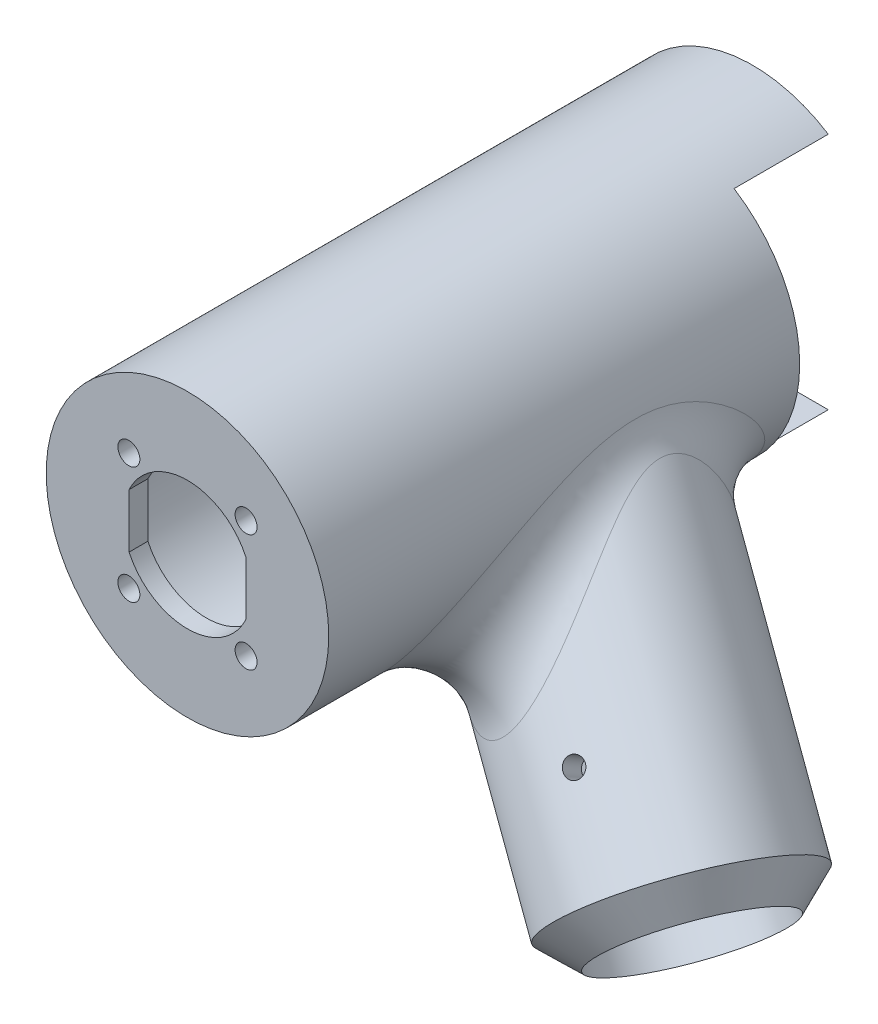
SolidWorks part; units mm, degrees
material "ABS"
ref_plane "Front Plane" through (0, 0, 0) normal (0, 0, 1) x (1, 0, 0)
ref_plane "Top Plane" through (0, 0, 0) normal (0, 1, 0) x (1, 0, 0)
ref_plane "Right Plane" through (0, 0, 0) normal (1, 0, 0) x (0, 0, -1)
sketch "Sketch1" plane through (0, 0, 0) normal (0, 0, 1) x (1, 0, 0)
  circle A0 centre (0, 0) radius 22.5
  dimension "D1" = 45
extrude "Boss-Extrude1" add sketch "Sketch1" along normal blind 90
sketch "Sketch2" plane through (0, 0, 0) normal (0, 0, -1) x (-1, 0, 0)
  circle A0 centre (0, 0) radius 16.2
  circle A1 centre (0, 0) radius 22.5 construction
  dimension "D1" = 6.3
extrude "Cut-Extrude1" cut sketch "Sketch2" against normal offset from surface (87 mm away) 3 up to face at (22.5, 0, 90)
sketch "Sketch3" plane through (0, 0, 0) normal (1, 0, 0) x (0, 0, -1)
  line L1 (15, -19) -> (-15, -19)
  line L2 (15, -19) -> (15, 19)
  line L3 (15, 19) -> (-15, 19)
  line L4 (-15, -19) -> (-15, 19)
  line L5 (15, -19) -> (-15, 19) construction
  line L6 (15, 19) -> (-15, -19) construction
  point P0 (0, 0)
  dimension "D1" = 15
  dimension "D2" = 38
extrude "Cut-Extrude2" cut sketch "Sketch3" along normal blind 33
sketch "Sketch4" plane through (0, 0, 0) normal (1, 0, 0) x (0, 0, -1)
  line L0 (0, 0) -> (-40, 0) construction
  line L1 (0, -22.5) -> (0, 22.5) construction
  line L2 (-10, 15) -> (-60, 15)
  line L3 (-10, 15) -> (-10, -15)
  line L4 (-10, -15) -> (-60, -15)
  line L5 (-60, 15) -> (-60, -15)
  line L6 (-10, 15) -> (-60, -15) construction
  line L7 (-10, -15) -> (-60, 15) construction
  point P2 (-35, 0)
  dimension "D1" = 50
  dimension "D2" = 10
  dimension "D3" = 30
ref_plane "Plane2" through (0, 0, 35) normal (0, 0, -1) x (-1, 0, 0)
sketch3d "3DSketch1"
  line L0 (0, 0, 35) -> (120, -120, 90)
sketch "Sketch5" plane through (0, 0, 35) normal (0, 0, -1) x (-1, 0, 0)
  line L0 (0, 0) -> (-54.3806, -54.3806)
  line L1 (0, 15) -> (0, -15) construction
  dimension "D1" = 45
ref_plane "Plane3" through (0, 0, 35) normal (0.6727, -0.6727, 0.3083) x (0.218, -0.218, -0.9513)
sketch "Sketch6" plane through (0, 0, 35) normal (0.6727, -0.6727, 0.3083) x (0.218, -0.218, -0.9513)
  circle A0 centre (0, 0) radius 17.5
  dimension "D1" = 35
extrude "Boss-Extrude2" add sketch "Sketch6" along normal blind 70
sketch "Sketch7" plane through (54.3448, -54.3448, 24.908) normal (0.6727, -0.6727, 0.3083) x (0.218, -0.218, -0.9513)
  circle A0 centre (-33.2951, 0) radius 12.9
  dimension "D1" = 25.8
extrude "Cut-Extrude3" cut sketch "Sketch7" against normal blind 50
sketch "Sketch8" plane through (0, 0, 0) normal (0, 0, -1) x (-1, 0, 0)
  circle A0 centre (0, 0) radius 19.5
extrude "Cut-Extrude4" cut sketch "Sketch8" against normal blind 61
fillet "Fillet1" radius 10 1 edges at (22.3843, 2.2789, 41.1361)
chamfer "Chamfer1" distance 5 angle 45 1 edges at (59.4607, -34.712, 56.5812)
ref_plane "Plane4" through (12.052, -19, 15) normal (0.7354, 0.6538, -0.178) x (-0.459, 0.2874, -0.8407)
sketch "Sketch9" plane through (12.052, -19, 15) normal (0.7354, 0.6538, -0.178) x (-0.459, 0.2874, -0.8407)
  line L0 (-55.3018, -12.6166) -> (-46.2319, -4.8898) construction
  line L1 (-43.9531, -25.9379) -> (-66.6504, 0.7047) construction
  line L2 (-5.8225, 29.5355) -> (-141.6207, -86.1531) construction
  circle A0 centre (-41.5998, -0.9437) radius 1.5
  dimension "D1" = 3
  dimension "D2" = 18
extrude "Cut-Extrude5" [suppressed] cut sketch "Sketch9" against normal blind 63
sketch "Sketch10" plane through (0, 0, 61) normal (0, 0, -1) x (-1, 0, 0)
  circle A0 centre (0, 0) radius 16.2 construction
  circle A1 centre (0, 0) radius 19.5
  circle A2 centre (0, 0) radius 19.5
  circle A3 centre (0, 0) radius 16.2
  dimension "D1" = 0
extrude "Boss-Extrude4" add sketch "Sketch10" along direction (0, 0, 1) on the side of the normal offset from surface (36 mm away) 25 up to face at (-6.3901, 0, 0)
sketch "Sketch11" plane through (0, 0, 87) normal (0, 0, -1) x (-1, 0, 0)
  line L0 (-9.3, -4.3096) -> (-9.3, 4.3096)
  line L1 (0, -10.25) -> (0, 13.1651) construction
  line L2 (9.3, -4.3096) -> (9.3, 4.3096)
  arc A0 (-9.3, -4.3096) -> (9.3, -4.3096) centre (0, 0) ccw
  arc A1 (9.3, 4.3096) -> (-9.3, 4.3096) centre (0, 0) ccw
  circle A2 centre (0, 13.2) radius 1.75
  circle A3 centre (9.3338, 9.3338) radius 1.75
  circle A4 centre (13.2, 0) radius 1.75
  circle A5 centre (9.3338, -9.3338) radius 1.75
  circle A6 centre (0, -13.2) radius 1.75
  circle A7 centre (-9.3338, -9.3338) radius 1.75
  circle A8 centre (-13.2, 0) radius 1.75
  circle A9 centre (-9.3338, 9.3338) radius 1.75
  dimension "D1" = 20.5
  dimension "D3" = 3.5
  dimension "D2" = 9.3
  dimension "D4" = 13.2
  dimension "D5" = 8
extrude "Cut-Extrude6" cut sketch "Sketch11" against normal blind 20.5 contours A7 | L0 A1 L2 A0 | A5 | A3 | A9 region at (9.3338, -9.3338, 87)
pattern_circular "CirPattern1" [suppressed] count 3 over 360 reverse direction yes of bodies 118
ref_plane "Plane5" through (54.0757, -54.0757, 24.7847) normal (0.6727, -0.6727, 0.3083) x (0.218, -0.218, -0.9513)
sketch "Sketch12" plane through (54.0757, -54.0757, 24.7847) normal (0.6727, -0.6727, 0.3083) x (0.218, -0.218, -0.9513)
  line L0 (-46.1951, 0) -> (-12.0884, 0) construction
  circle A0 centre (-33.2951, 0) radius 12.9 construction
ref_axis "Axis1" through (25.876, -25.876, 46.8598) along (0.6727, -0.6727, 0.3083)
ref_plane "Plane6" through (0, 0, 0) normal (-0.7071, -0.7071, 0) x (-0.7071, 0.7071, 0)
sketch "Sketch14" plane through (0, 0, 0) normal (-0.7071, -0.7071, 0) x (-0.7071, 0.7071, 0)
  line L0 (0, -35) -> (-169.7056, -90) construction
  line L1 (-62.2325, -68.7295) -> (-72.7477, -36.2843) construction
  circle A0 centre (-47.1839, -50.2919) radius 1.5
  dimension "D1" = 3
  dimension "D2" = 20
extrude "Cut-Extrude7" cut sketch "Sketch14" along normal blind 40
pattern_circular "CirPattern2" count 3 over 360 about axis through (13.4532, -13.4532, 41.1661) along (0.6727, -0.6727, 0.3083) of "Cut-Extrude7" reverse direction yes
